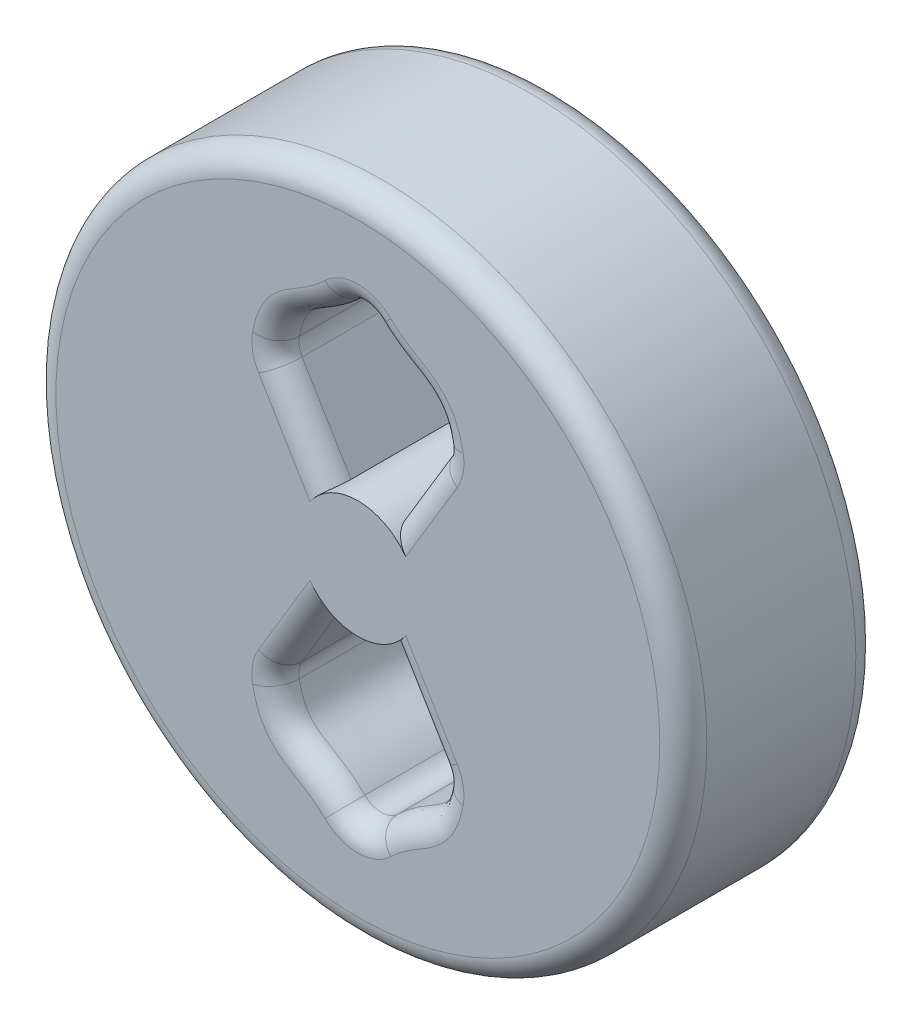
SolidWorks part; units mm, degrees
ref_plane "Front Plane" through (0, 0, 0) normal (0, 0, 1) x (1, 0, 0)
ref_plane "Top Plane" through (0, 0, 0) normal (0, 1, 0) x (1, 0, 0)
ref_plane "Right Plane" through (0, 0, 0) normal (1, 0, 0) x (0, 0, -1)
sketch "Sketch1" plane through (0, 0, 0) normal (0, 0, 1) x (1, 0, 0)
  circle A0 centre (0, 0) radius 889
  dimension "D1" = 1778
extrude "Boss-Extrude1" add sketch "Sketch1" along normal blind 635 contours A0
sketch "Sketch2" plane through (0, 0, 635) normal (0, 0, 1) x (1, 0, 0)
  line L0 (0, 0) -> (-270.5259, 450.6098)
  line L1 (0, 0) -> (0, 762) construction
  line L2 (0, 762) -> (-136.7209, 575.8499) construction
  line L3 (-136.7209, 575.8499) -> (-247.9515, 650.0036) construction
  line L4 (-247.9515, 650.0036) -> (-270.5259, 450.6098) construction
  line L5 (0, 0) -> (270.5259, 450.6098)
  line L6 (0, 762) -> (136.7209, 575.8499) construction
  line L7 (136.7209, 575.8499) -> (247.9515, 650.0036) construction
  line L8 (247.9515, 650.0036) -> (270.5259, 450.6098) construction
  spline S0 degree 3 poles (0, 762) (-136.7209, 575.8499) (-247.9515, 650.0036) (-270.5259, 450.6098) knots 0 0 0 0 1 1 1 1
  spline S1 degree 3 poles (0, 762) (136.7209, 575.8499) (247.9515, 650.0036) (270.5259, 450.6098) knots 0 0 0 0 1 1 1 1
extrude "Cut-Extrude1" cut sketch "Sketch2" against normal blind 635
fillet "Fillet1" radius 76.2 4 edges at (0, 762, 317.5) (0, 0, 317.5) (270.5259, 450.6098, 317.5) (-270.5259, 450.6098, 317.5)
sketch "Sketch3" plane through (0, 0, 0) normal (0, 1, 0) x (1, 0, 0)
  line L0 (0, 0) -> (0, -635) construction
  line L1 (-889, -635) -> (889, -635) construction
pattern_circular "CirPattern2" count 2 over 360 about axis through (0, 0, 0) along (0, 0, 1) of "Cut-Extrude1", "Fillet1"
fillet "Fillet2" radius 76.2 32 edges at (266.2037, -453.0234, 635) (0, -721.7822, 635) (-266.2037, -453.0234, 635) (-160.9368, -268.0692, 635) (0, -71.8417, 635) (0, 71.8417, 635) (-160.9368, 268.0692, 635) (-266.2037, 453.0234, 635) (0, 721.7822, 635) (266.2037, 453.0234, 635) (266.2037, -453.0234, 0) (0, -721.7822, 0) (-266.2037, -453.0234, 0) (-160.9368, -268.0692, 0) (0, -71.8417, 0) (-266.2037, 453.0234, 0) (0, 721.7822, 0) (266.2037, 453.0234, 0) (160.9368, 268.0692, 0) (0, 71.8417, 0) (160.9368, -268.0692, 635) (160.9368, 268.0692, 635) (160.9368, -268.0692, 0) (-160.9368, 268.0692, 0)
sketch "Sketch4" plane through (0, 0, 635) normal (0, 0, 1) x (1, 0, 0)
  circle A0 centre (0, 0) radius 190.5
  dimension "D1" = 381
extrude "Boss-Extrude2" add sketch "Sketch4" against normal blind 889 contours A0
sketch "Sketch5" plane through (0, 0, 0) normal (1, 0, 0) x (0, 0, -1)
  line L0 (0, 0) -> (1014.1189, 0) construction
  line L1 (-635, 889) -> (0, 889)
  line L2 (-635, 889) -> (-635, 977.9)
  line L3 (-558.8, 1054.1) -> (-76.2, 1054.1)
  line L4 (0, 889) -> (0, 977.9)
  arc A0 (-76.2, 1054.1) -> (0, 977.9) centre (-76.2, 977.9) cw
  arc A1 (-635, 977.9) -> (-558.8, 1054.1) centre (-558.8, 977.9) cw
  point P7 (0, 1054.1)
  dimension "D2" = 76.2
  dimension "D1" = 165.1
revolve "Revolve1" add sketch "Sketch5" angle 360 about L0
sketch "Sketch6" plane through (0, 0, -254) normal (0, 0, -1) x (-1, 0, 0)
  circle A0 centre (0, 0) radius 50.8
  dimension "D1" = 101.6
extrude "Cut-Extrude3" cut sketch "Sketch6" against normal blind 88.9
scale "Scale3" scale about centroid uniform scaling yes scale factor 0.125
